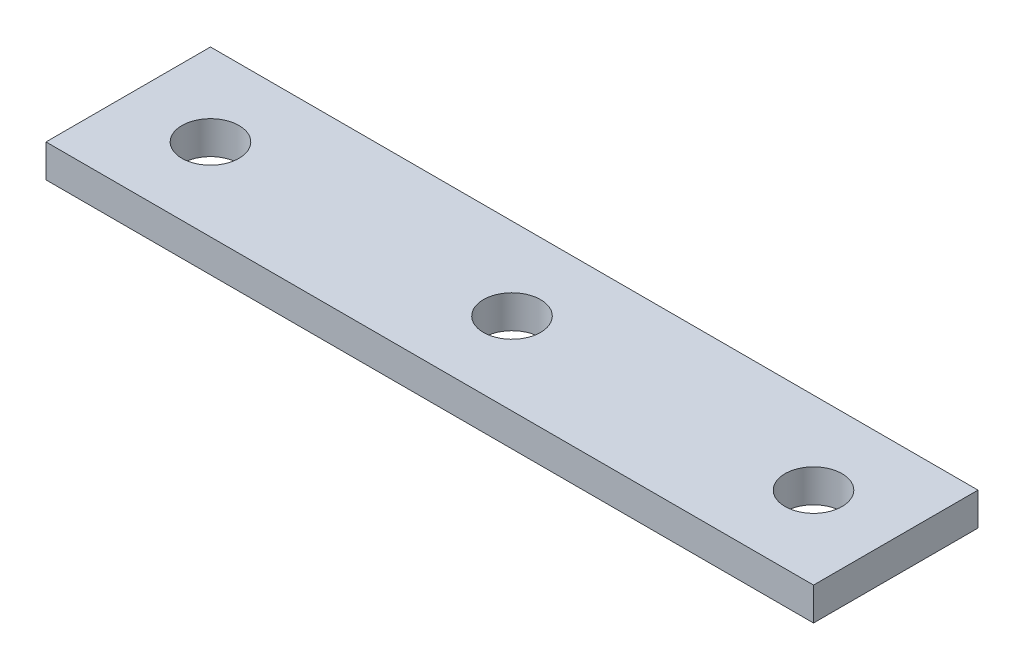
SolidWorks part; units mm, degrees
ref_plane "Спереди" through (0, 0, 0) normal (0, 0, 1) x (1, 0, 0)
ref_plane "Сверху" through (0, 0, 0) normal (0, 1, 0) x (1, 0, 0)
ref_plane "Справа" through (0, 0, 0) normal (1, 0, 0) x (0, 0, -1)
sketch "Эскиз1" plane through (0, 0, 0) normal (0, 1, 0) x (1, 0, 0)
  line L1 (-35, 7.5) -> (35, 7.5)
  line L2 (-35, 7.5) -> (-35, -7.5)
  line L3 (-35, -7.5) -> (35, -7.5)
  line L4 (35, 7.5) -> (35, -7.5)
  line L5 (-35, 7.5) -> (35, -7.5) construction
  line L6 (-35, -7.5) -> (35, 7.5) construction
  circle A0 centre (0, 0) radius 2.6
  circle A1 centre (27.5, 0) radius 2.6
  circle A2 centre (-27.5, 0) radius 2.6
  point P0 (0, 0)
  point P12 (0, 0)
extrude "Бобышка-Вытянуть1" add sketch "Эскиз1" along normal blind 3
